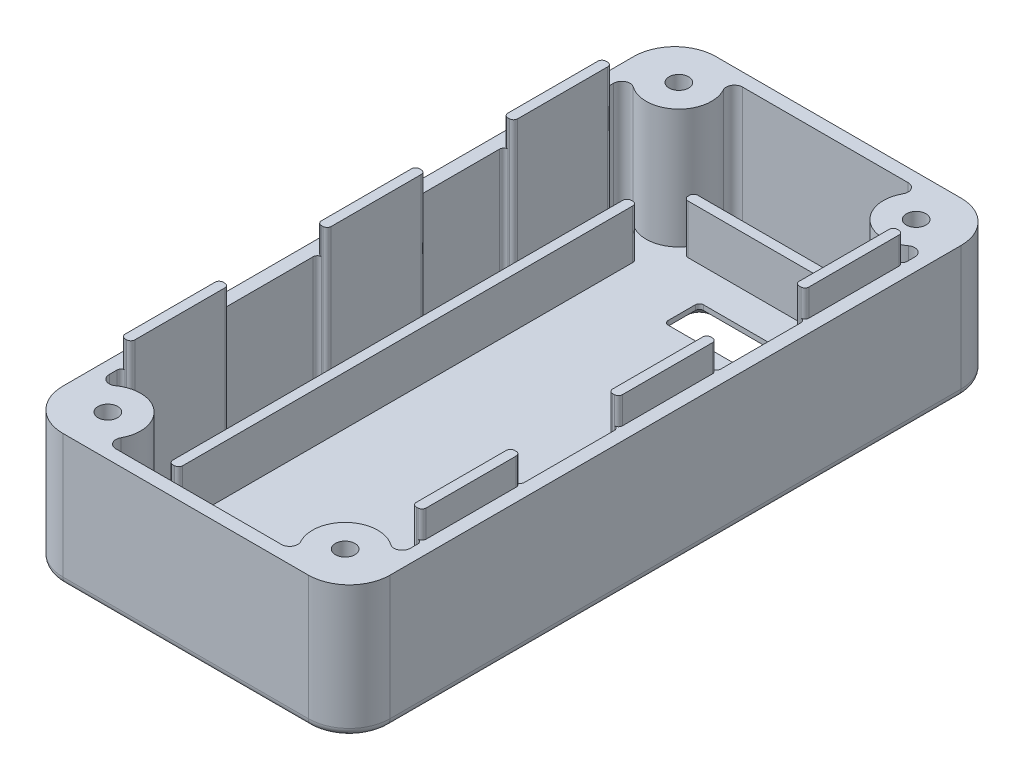
SolidWorks part; units mm, degrees
ref_plane "Front Plane" through (0, 0, 0) normal (0, 0, 1) x (1, 0, 0)
ref_plane "Top Plane" through (0, 0, 0) normal (0, 1, 0) x (1, 0, 0)
ref_plane "Right Plane" through (0, 0, 0) normal (1, 0, 0) x (0, 0, -1)
sketch "Base Sketch" plane through (0, 0, 0) normal (0, 1, 0) x (1, 0, 0)
  line L1 (0, 0) -> (40, 0)
  line L2 (0, 0) -> (0, 79.79)
  line L3 (0, 79.79) -> (40, 79.79)
  line L4 (40, 0) -> (40, 79.79)
extrude "Base" add sketch "Base Sketch" along normal blind 16.2
fillet "Corner Rounds R5" radius 5 4 edges at (0, 8.1, -79.79) (40, 8.1, -79.79) (40, 8.1, 0) (0, 8.1, 0)
shell "Shell" thickness 1.6 removed face at (20, 16.2, -39.895)
sketch "Sketch2" plane through (0, 0, 0) normal (0, 1, 0) x (1, 0, 0)
  circle A0 centre (5.5, 5) radius 4
  circle A1 centre (34.5, 5) radius 4
  circle A2 centre (5.5, 74.79) radius 4
  circle A3 centre (34.5, 74.79) radius 4
extrude "Screw Bosses" add sketch "Sketch2" along normal blind 16.2
sketch "Sketch3" plane through (0, 0, 0) normal (0, 1, 0) x (1, 0, 0)
  line L1 (1.6, 10.5) -> (2.8, 10.5)
  line L2 (1.6, 10.5) -> (1.6, 22.5)
  line L3 (1.6, 22.5) -> (2.8, 22.5)
  line L4 (2.8, 10.5) -> (2.8, 22.5)
  line L6 (1.6, 34.5) -> (2.8, 34.5)
  line L7 (1.6, 34.5) -> (1.6, 46.5)
  line L8 (1.6, 46.5) -> (2.8, 46.5)
  line L9 (2.8, 34.5) -> (2.8, 46.5)
  line L11 (1.6, 57.29) -> (2.8, 57.29)
  line L12 (1.6, 57.29) -> (1.6, 69.29)
  line L13 (1.6, 69.29) -> (2.8, 69.29)
  line L14 (2.8, 57.29) -> (2.8, 69.29)
  line L16 (37.2, 10.5) -> (38.4, 10.5)
  line L17 (37.2, 10.5) -> (37.2, 22.5)
  line L18 (37.2, 22.5) -> (38.4, 22.5)
  line L19 (38.4, 10.5) -> (38.4, 22.5)
  line L21 (37.2, 34.5) -> (38.4, 34.5)
  line L22 (37.2, 34.5) -> (37.2, 46.5)
  line L23 (37.2, 46.5) -> (38.4, 46.5)
  line L24 (38.4, 34.5) -> (38.4, 46.5)
  line L26 (37.2, 57.29) -> (38.4, 57.29)
  line L27 (37.2, 57.29) -> (37.2, 69.29)
  line L28 (37.2, 69.29) -> (38.4, 69.29)
  line L29 (38.4, 57.29) -> (38.4, 69.29)
extrude "Alignment Tabs" add sketch "Sketch3" along normal blind 19.5
fillet "Bottom Edge Round R1" radius 1 8 edges at (1.4645, 0, -1.4645) (20, 0, 0) (38.5355, 0, -1.4645) (40, 0, -39.895) (38.5355, 0, -78.3255) (20, 0, -79.79) (1.4645, 0, -78.3255) (0, 0, -39.895)
sketch "Sketch4" plane through (0, 0, 0) normal (0, 1, 0) x (1, 0, 0)
  circle A0 centre (5.5, 5) radius 1.2
  circle A1 centre (34.5, 5) radius 1.2
  circle A2 centre (5.5, 74.79) radius 1.2
  circle A3 centre (34.5, 74.79) radius 1.2
extrude "M2 Clearance Holes" cut sketch "Sketch4" along normal through all
sketch "Sketch5" plane through (0, 0, 0) normal (0, 1, 0) x (1, 0, 0)
  circle A0 centre (5.5, 5) radius 2.2
  circle A1 centre (34.5, 5) radius 2.2
  circle A2 centre (5.5, 74.79) radius 2.2
  circle A3 centre (34.5, 74.79) radius 2.2
extrude "M2 Counterbores" cut sketch "Sketch5" along normal blind 12.2
sketch "Slide Switch Cutout Sketch" plane through (0, 0, 0) normal (0, 1, 0) x (1, 0, 0)
  line L0 (16.2, 63.4) -> (23.8, 63.4)
  line L1 (23.8, 63.4) -> (23.8, 67)
  line L2 (23.8, 67) -> (16.2, 67)
  line L3 (16.2, 67) -> (16.2, 63.4)
extrude "Slide Switch Cutout" cut sketch "Slide Switch Cutout Sketch" along normal blind 2
sketch "2xAAA Guide Rails Sketch" plane through (0, 0, 0) normal (0, 1, 0) x (1, 0, 0)
  line L0 (32.85, 12) -> (34.05, 12)
  line L1 (34.05, 12) -> (34.05, 68)
  line L2 (34.05, 68) -> (32.85, 68)
  line L3 (32.85, 68) -> (32.85, 12)
  line L4 (5.95, 12) -> (7.15, 12)
  line L5 (7.15, 12) -> (7.15, 68)
  line L6 (7.15, 68) -> (5.95, 68)
  line L7 (5.95, 68) -> (5.95, 12)
extrude "2xAAA Guide Rails" add sketch "2xAAA Guide Rails Sketch" along normal blind 7.6
sketch "2xAAA End Rails Sketch" plane through (0, 0, 0) normal (0, 1, 0) x (1, 0, 0)
  line L0 (9.5, 7.2) -> (30.5, 7.2)
  line L1 (30.5, 7.2) -> (30.5, 8.4)
  line L2 (30.5, 8.4) -> (9.5, 8.4)
  line L3 (9.5, 8.4) -> (9.5, 7.2)
  line L4 (9.5, 71.4) -> (30.5, 71.4)
  line L5 (30.5, 71.4) -> (30.5, 72.6)
  line L6 (30.5, 72.6) -> (9.5, 72.6)
  line L7 (9.5, 72.6) -> (9.5, 71.4)
extrude "2xAAA End Rails" add sketch "2xAAA End Rails Sketch" along normal blind 7.6
chamfer "Rail Buttress Chamfers 3x45" distance 3 angle 45 4 edges at (20, 1.6, -72.6) (20, 1.6, -7.2) (5.95, 1.6, -40) (34.05, 1.6, -40) tangent propagation no
fillet "Lug Junction Fillets R1" radius 1 8 edges at (32.3929, 8.9, -78.19) (38.4, 8.9, -73.9012) (7.6071, 8.9, -78.19) (1.6, 8.9, -73.9012) (32.3929, 8.9, -1.6) (38.4, 8.9, -5.8888) (7.6071, 8.9, -1.6) (1.6, 8.9, -5.8888)
chamfer "Chamfer2" distance 1 angle 45 4 edges at (5.5, 12.2, -2.8) (34.5, 12.2, -2.8) (34.5, 12.2, -72.59) (5.5, 12.2, -72.59)
fillet "Fillet2" radius 0.5 44 edges at (37.2, 10.55, -69.29) (38.4, 8.9, -69.29) (32.85, 4.6, -68) (32.85, 4.6, -12) (30.5, 4.6, -71.4) (30.5, 4.6, -8.4) (9.5, 4.6, -71.4) (9.5, 4.6, -8.4) (7.15, 4.6, -68) (7.15, 4.6, -12) (34.05, 6.1, -68) (34.05, 6.1, -12) (30.5, 6.1, -72.6) (30.5, 6.1, -7.2) (9.5, 6.1, -72.6) (9.5, 6.1, -7.2) (5.95, 6.1, -68) (5.95, 6.1, -12) (23.8, 0.8, -67) (23.8, 0.8, -63.4) (16.2, 0.8, -67) (16.2, 0.8, -63.4) (37.2, 10.55, -57.29) (37.2, 10.55, -46.5) (37.2, 10.55, -34.5) (37.2, 10.55, -22.5) (37.2, 10.55, -10.5) (2.8, 10.55, -69.29) (2.8, 10.55, -57.29) (2.8, 10.55, -46.5) (2.8, 10.55, -34.5) (2.8, 10.55, -22.5) (2.8, 10.55, -10.5) (38.4, 8.9, -57.29) (38.4, 8.9, -46.5) (38.4, 8.9, -34.5) (38.4, 8.9, -22.5) (38.4, 8.9, -10.5) (1.6, 8.9, -69.29) (1.6, 8.9, -57.29) (1.6, 8.9, -46.5) (1.6, 8.9, -34.5) (1.6, 8.9, -22.5) (1.6, 8.9, -10.5)
fillet "Tab Top Corner Fillets R0.5" radius 0.5 12 edges at (38.4, 17.85, -57.29) (38.4, 17.85, -69.29) (38.4, 17.85, -34.5) (38.4, 17.85, -46.5) (38.4, 17.85, -10.5) (38.4, 17.85, -22.5) (1.6, 17.85, -57.29) (1.6, 17.85, -69.29) (1.6, 17.85, -34.5) (1.6, 17.85, -46.5) (1.6, 17.85, -22.5) (1.6, 17.85, -10.5)
sketch "Slide Switch Slot Sketch" plane through (0, 0, 0) normal (0, 1, 0) x (1, 0, 0)
  line L0 (15.94, 63.04) -> (24.06, 63.04)
  line L1 (24.56, 63.54) -> (24.56, 66.86)
  line L2 (24.06, 67.36) -> (15.94, 67.36)
  line L3 (15.44, 66.86) -> (15.44, 63.54)
  arc A0 (24.06, 63.04) -> (24.56, 63.54) centre (24.06, 63.54) ccw
  arc A1 (24.56, 66.86) -> (24.06, 67.36) centre (24.06, 66.86) ccw
  arc A2 (15.94, 67.36) -> (15.44, 66.86) centre (15.94, 66.86) ccw
  arc A3 (15.44, 63.54) -> (15.94, 63.04) centre (15.94, 63.54) ccw
extrude "Slide Switch Slot +20% 9.12x4.32" cut sketch "Slide Switch Slot Sketch" along normal through all
chamfer "Slot Chamfer 1x45 (support-free)" distance 1 angle 45 8 edges at (15.5864, 0, -63.1864) (20, 0, -63.04) (24.4136, 0, -63.1864) (24.56, 0, -65.2) (24.4136, 0, -67.2136) (20, 0, -67.36) (15.5864, 0, -67.2136) (15.44, 0, -65.2)
